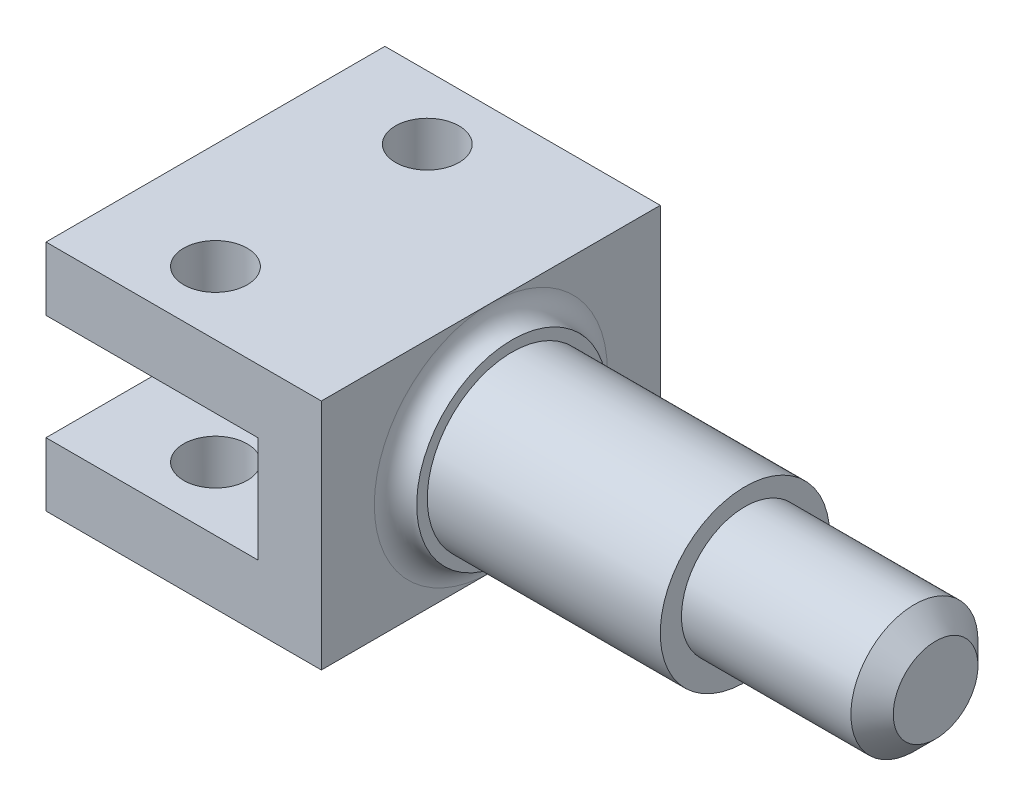
SolidWorks part; units mm, degrees
material "6061 合金"
ref_plane "前视基准面" through (0, 0, 0) normal (0, 0, 1) x (1, 0, 0)
ref_plane "上视基准面" through (0, 0, 0) normal (0, 1, 0) x (1, 0, 0)
ref_plane "右视基准面" through (0, 0, 0) normal (1, 0, 0) x (0, 0, -1)
sketch "草图1" plane through (0, 0, 0) normal (0, 0, 1) x (1, 0, 0)
  line L0 (0, 0) -> (13, 0)
  line L1 (13, 0) -> (13, 11)
  line L2 (13, 11) -> (0, 11)
  line L3 (0, 11) -> (0, 8)
  line L4 (0, 8) -> (10, 8)
  line L5 (10, 8) -> (10, 3)
  line L6 (10, 3) -> (0, 3)
  line L7 (0, 3) -> (0, 0)
  dimension "D1" = 13
  dimension "D2" = 11
  dimension "D3" = 3
  dimension "D4" = 10
  dimension "D5" = 5
extrude "凸台-拉伸1" add sketch "草图1" along normal blind 16
sketch "草图2" plane through (0, 11, 0) normal (0, 1, 0) x (1, 0, 0)
  line L0 (5, 0) -> (5, -16) construction
  line L1 (13, 0) -> (0, 0) construction
  line L2 (13, -16) -> (0, -16) construction
  line L3 (0, -16) -> (0, 0) construction
  line L4 (0, -8) -> (13, -8) construction
  line L5 (13, -16) -> (13, 0) construction
  circle A0 centre (5, -3) radius 1.5
  circle A1 centre (5, -13) radius 1.5
  dimension "D2" = 3
  dimension "D3" = 3
  dimension "D1" = 5
extrude "切除-拉伸1" cut sketch "草图2" against normal blind 16
sketch "草图3" plane through (13, 0, 0) normal (1, 0, 0) x (0, 0, -1)
  line L0 (-16, 0) -> (0, 0) construction
  line L1 (-16, 0) -> (-16, 11) construction
  circle A1 centre (-8, 5.5) radius 4.5
  dimension "D1" = 9
  dimension "D2" = 5.5
  dimension "D3" = 8
extrude "凸台-拉伸2" add sketch "草图3" along normal blind 1
fillet "圆角1" radius 1 1 edges at (13, 5.5, 3.5)
sketch "草图4" plane through (14, 0, 0) normal (1, 0, 0) x (0, 0, -1)
  circle A0 centre (-8, 5.5) radius 4
  dimension "D1" = 8
extrude "凸台-拉伸3" add sketch "草图4" along normal blind 11
sketch "草图5" plane through (25, 0, 0) normal (1, 0, 0) x (0, 0, -1)
  circle A0 centre (-8, 5.6833) radius 3
  dimension "D1" = 6
extrude "凸台-拉伸4" add sketch "草图5" along normal blind 9
chamfer "倒角1" distance 1 angle 45 1 edges at (34, 5.6833, 5)
